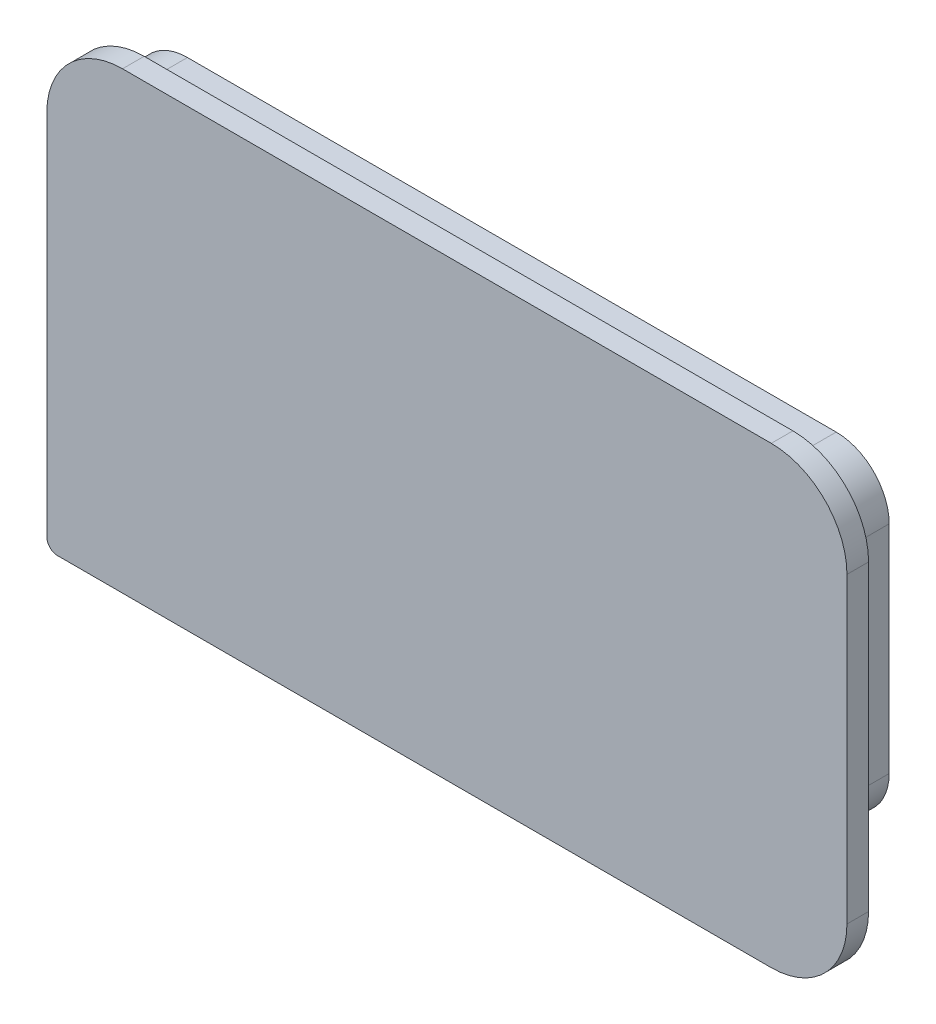
SolidWorks part; units mm, degrees
ref_plane "Front Plane" through (0, 0, 0) normal (0, 0, 1) x (1, 0, 0)
ref_plane "Top Plane" through (0, 0, 0) normal (0, 1, 0) x (1, 0, 0)
ref_plane "Right Plane" through (0, 0, 0) normal (1, 0, 0) x (0, 0, -1)
sketch "Sketch1" plane through (0, 0, 0) normal (0, 0, 1) x (1, 0, 0)
  line L1 (37, -21) -> (-37, -21)
  line L2 (37, -21) -> (37, 21)
  line L3 (37, 21) -> (-37, 21)
  line L4 (-37, -21) -> (-37, 21)
  line L5 (37, -21) -> (-37, 21) construction
  line L6 (37, 21) -> (-37, -21) construction
  point P0 (0, 0)
  dimension "D1" = 74
  dimension "D2" = 42
extrude "Boss-Extrude1" add sketch "Sketch1" along normal blind 2
sketch "Sketch2" plane through (0, 0, 0) normal (0, 0, -1) x (-1, 0, 0)
  line L10 (37, 21) -> (-37, 21)
  line L11 (37, -21) -> (37, 21)
  line L12 (35, -21) -> (37, -21)
  line L13 (35, 19) -> (35, -21)
  line L14 (-35, 19) -> (35, 19)
  line L15 (-35, -11) -> (-35, 19)
  line L16 (-5, -11) -> (-35, -11)
  line L17 (-5, -21) -> (-5, -11)
  line L18 (-37, -21) -> (-5, -21)
  line L19 (-37, 21) -> (-37, -21)
  line L20 (37, 21) -> (-37, 21)
  line L21 (37, -21) -> (37, 21)
  line L22 (35, -21) -> (37, -21)
  line L23 (35, 19) -> (35, -21)
  line L24 (-35, 19) -> (35, 19)
  line L25 (-35, -11) -> (-35, 19)
  line L26 (-5, -11) -> (-35, -11)
  line L27 (-5, -21) -> (-5, -11)
  line L28 (-37, -21) -> (-5, -21)
  line L29 (-37, 21) -> (-37, -21)
  dimension "D1" = 0
extrude "Boss-Extrude2" add sketch "Sketch2" along normal blind 5
fillet "Fillet2" radius 5 4 edges at (-35, 19, -2.5) (35, 19, -2.5) (35, -11, -2.5) (5, -11, -2.5)
fillet "Fillet3" radius 5 9 edges at (5, -18.5, 0) (6.4645, -12.4645, 0) (20, -11, 0) (33.5355, -9.5355, 0) (35, 4, 0) (33.5355, 17.5355, 0) (-35, -3.5, 0) (-33.5355, 17.5355, 0) (0, 19, 0)
fillet "Fillet4" radius 7 3 edges at (37, -21, -1.5) (37, 21, -1.5) (-37, 21, -1.5)
sketch "Sketch3" plane through (0, 0, 0) normal (0, 0, -1) x (-1, 0, 0)
  line L0 (37.1, 21.1) -> (-37.1, 21.1)
  line L1 (-37.1, 21.1) -> (-37.1, -21.1)
  line L2 (-37.1, -21.1) -> (-6, -21.1)
  line L3 (-4.9, -20) -> (-4.9, -16)
  line L4 (-10, -10.9) -> (-30, -10.9)
  line L5 (-34.9, -6) -> (-34.9, 14)
  line L6 (-30, 18.9) -> (30, 18.9)
  line L7 (34.9, 14) -> (34.9, -20)
  line L8 (36, -21.1) -> (37.1, -21.1)
  line L9 (37.1, -21.1) -> (37.1, 21.1)
  line L10 (37, 21) -> (-37, 21)
  line L11 (-37, 21) -> (-37, -21)
  line L12 (-37, -21) -> (-5, -21)
  line L13 (-5, -21) -> (-5, -11)
  line L14 (-5, -11) -> (-35, -11)
  line L15 (-35, -11) -> (-35, 19)
  line L16 (-35, 19) -> (35, 19)
  line L17 (35, 19) -> (35, -21)
  line L18 (35, -21) -> (37, -21)
  line L19 (37, -21) -> (37, 21)
  line L20 (37, 21) -> (-37, 21) construction
  line L21 (-37, 21) -> (-37, -21) construction
  line L22 (-37, -21) -> (-6, -21) construction
  line L23 (-5, -20) -> (-5, -16) construction
  line L24 (-10, -11) -> (-30, -11) construction
  line L25 (-35, -6) -> (-35, 14) construction
  line L26 (-30, 19) -> (30, 19) construction
  line L27 (35, 14) -> (35, -20) construction
  line L28 (36, -21) -> (37, -21) construction
  line L29 (37, -21) -> (37, 21) construction
  arc A0 (30, 19) -> (35, 14) centre (30, 14) cw construction
  arc A1 (-30, -11) -> (-35, -6) centre (-30, -6) cw construction
  arc A2 (-35, 14) -> (-30, 19) centre (-30, 14) cw construction
  arc A3 (-5, -16) -> (-10, -11) centre (-10, -16) ccw construction
  arc A4 (35, -20) -> (36, -21) centre (36, -20) ccw construction
  arc A5 (-6, -21) -> (-5, -20) centre (-6, -20) ccw construction
  arc A6 (-6, -21.1) -> (-4.9, -20) centre (-6, -20) ccw
  arc A7 (-4.9, -16) -> (-10, -10.9) centre (-10, -16) ccw
  arc A8 (-30, -10.9) -> (-34.9, -6) centre (-30, -6) cw
  arc A9 (-34.9, 14) -> (-30, 18.9) centre (-30, 14) cw
  arc A10 (30, 18.9) -> (34.9, 14) centre (30, 14) cw
  arc A11 (34.9, -20) -> (36, -21.1) centre (36, -20) ccw
  dimension "D2" = 5
  dimension "D3" = 5
  dimension "D4" = 1
  dimension "D1" = 0
  dimension "D5" = 0.1
extrude "Cut-Extrude2" cut sketch "Sketch3" along normal up to surface (5 mm away) up to face at (4.7912, -0.1458, -5)
fillet "Fillet6" radius 1 1 edges at (-37, -21, 1)
